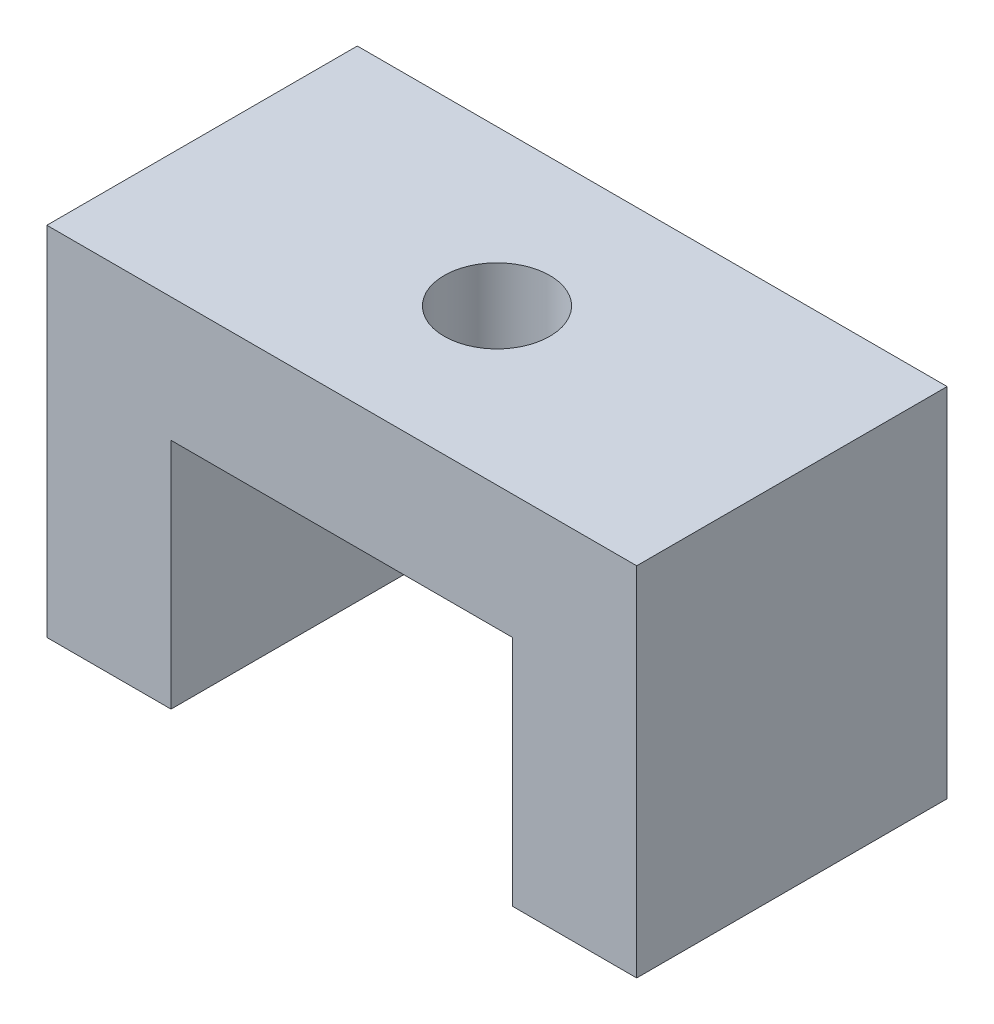
SolidWorks part; units mm, degrees
ref_plane "Plan de face" through (0, 0, 0) normal (0, 0, 1) x (1, 0, 0)
ref_plane "Plan de dessus" through (0, 0, 0) normal (0, 1, 0) x (1, 0, 0)
ref_plane "Plan de droite" through (0, 0, 0) normal (1, 0, 0) x (0, 0, -1)
sketch "Esquisse1" plane through (0, 0, 0) normal (0, 1, 0) x (1, 0, 0)
  line L0 (-19, 10) -> (-19, -10)
  line L1 (0, 0) -> (11, 0) construction
  line L2 (0, 0) -> (-11, 0) construction
  line L3 (0, 0) -> (11, 0) construction
  line L4 (-11, 0) -> (-11, 10)
  line L5 (-11, 10) -> (-19, 10)
  line L7 (-19, -10) -> (-11, -10)
  line L8 (-11, -10) -> (-11, 0)
  line L9 (11, 0) -> (11, 10)
  line L10 (11, 10) -> (19, 10)
  line L12 (19, -10) -> (11, -10)
  line L13 (11, -10) -> (11, 0)
  line L14 (19, -10) -> (19, 10)
  circle A0 centre (-15, 0) radius 2
  circle A1 centre (15, 0) radius 2
  dimension "D1" = 8
  dimension "D7" = 4
  dimension "D8" = 4
  dimension "D2" = 11
  dimension "D3" = 11
  dimension "D4" = 8
  dimension "D5" = 20
  dimension "D6" = 20
extrude "Boss.-Extru.1" add sketch "Esquisse1" along normal blind 15 contours A0 | A1 | L13 L12 L14 L10 L9 A1 | L7 L8 L4 L5 L0 A0 region at (-15, 0, -9.7846) region at (11.2154, 0, -5) region at (-15, 0, 0) region at (15, 0, 0)
sketch "Esquisse3" plane through (0, 15, 0) normal (0, 1, 0) x (1, 0, 0)
  line L0 (-19, -10) -> (19, -10)
  line L1 (19, -10) -> (19, 10)
  line L2 (19, 10) -> (19, -10) construction
  line L3 (19, 10) -> (-19, 10)
  line L4 (-19, 10) -> (-19, -10)
  dimension "D1" = 38
  dimension "D2" = 20
extrude "Boss.-Extru.2" add sketch "Esquisse3" along normal blind 8
sketch "Esquisse4" plane through (0, 23, 0) normal (0, 1, 0) x (1, 0, 0)
  circle A0 centre (0, 0) radius 3.4
  dimension "D1" = 6.8
extrude "Enlèv. mat.-Extru.1" cut sketch "Esquisse4" against normal blind 10
extrude "Enlèv. mat.-Extru.3" cut sketch "Esquisse1<3>" along normal blind 15 contours A0 | A1 region at (-15, 0, 0) region at (15, 0, 0)
sketch "Esquisse1<3>" plane through (0, 0, 0) normal (0, 1, 0) x (1, 0, 0) same geometry as "Esquisse1"
